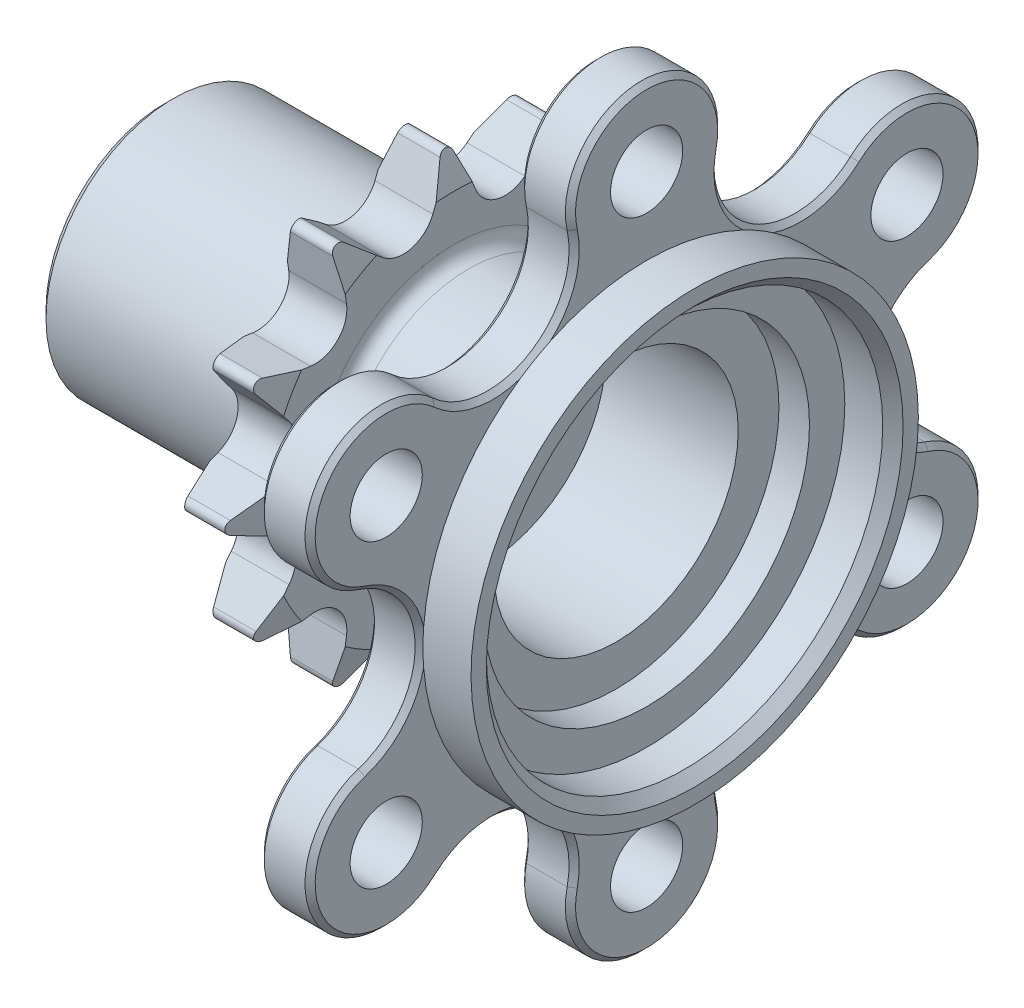
SolidWorks part; units mm, degrees
note: '?' marks a value the reader was unsure of.
material "AISI 4130 Steel, annealed at 865C"
ref_plane "X-Y Datum" through (0, 0, 0) normal (0, 0, 1) x (1, 0, 0)
ref_plane "X-Z Datum" through (0, 0, 0) normal (0, 1, 0) x (1, 0, 0)
ref_plane "Y-Z Datum" through (0, 0, 0) normal (1, 0, 0) x (0, 0, -1)
sketch "Sketch1" plane through (0, 0, 0) normal (1, 0, 0) x (0, 0, -1)
  circle A0 centre (0, 0) radius 47
  dimension "D1" = 94
extrude "Base-Extrude" add sketch "Sketch1" against normal blind 6.35
hole_wizard "M8 Clearance Holes" positions "Sketch5" profile "Sketch7" hole size "M8" standard "ANSI Metric" end condition through all
sketch "Sketch5" plane through (0, 0, 0) normal (1, 0, 0) x (0, 0, -1)
  point P0 (0, -37.5)
  dimension "D1" = 37.5
sketch "Sketch7" plane through (0, -37.5, 0) normal (0, 1, 0) x (0, 0, -1)
  line L0 (0, 0) -> (0, 6.35)
  line L1 (0, 6.35) -> (4.5, 6.35)
  line L2 (4.5, 6.35) -> (4.5, 0)
  line L5 (4.5, 0) -> (0, 0)
  line L11 (0, -6.35) -> (0, 107.95) construction
  dimension "Thru Hole Dia." = 9
  dimension "Thru Hole Depth" = 6.35
pattern_circular "CirPattern" count 6 over 360 about axis through (0, 0, 0) along (1, 0, 0) of "M8 Clearance Holes"
sketch "Sketch19" plane through (0, 0, 0) normal (1, 0, 0) x (0, 0, -1)
  line L0 (0, 37.5) -> (32.476, 18.75) construction
  circle A0 centre (0, 37.5) radius 9.5
  circle A1 centre (32.476, 18.75) radius 9.5
  circle A2 centre (0, 0) radius 47 construction
  arc A3 (9.2748, 35.4439) -> (26.0579, 25.7542) centre (19.194, 33.245) ccw
  circle A4 centre (32.476, 18.75) radius 9.5
  circle A5 centre (32.476, -18.75) radius 9.5
  arc A6 (35.3328, 9.6897) -> (35.3328, -9.6897) centre (38.3881, 0) ccw
  circle A7 centre (32.476, -18.75) radius 9.5
  circle A8 centre (0, -37.5) radius 9.5
  arc A9 (26.0579, -25.7542) -> (9.2748, -35.4439) centre (19.194, -33.245) ccw
  circle A10 centre (0, -37.5) radius 9.5
  circle A11 centre (-32.476, -18.75) radius 9.5
  arc A12 (-9.2748, -35.4439) -> (-26.0579, -25.7542) centre (-19.194, -33.245) ccw
  circle A13 centre (-32.476, -18.75) radius 9.5
  circle A14 centre (-32.476, 18.75) radius 9.5
  arc A15 (-35.3328, -9.6897) -> (-35.3328, 9.6897) centre (-38.3881, 0) ccw
  circle A16 centre (-32.476, 18.75) radius 9.5
  circle A17 centre (0, 37.5) radius 9.5
  arc A18 (-26.0579, 25.7542) -> (-9.2748, 35.4439) centre (-19.194, 33.245) ccw
  circle A19 centre (-32.476, 18.75) radius 4.5 construction
  circle M12 centre (0, 0) radius 47
  dimension "D1" = 10.16
  dimension "D2" = 6
extrude "Cut-Extrude" cut sketch "Sketch19" against normal through all both and the other way through all contours A16 A18 A0 M12 | A0 A3 A1 M12 | A13 A15 A14 M12 | A4 A6 A5 M12 | A7 A9 A8 M12 | A10 A12 A11 M12 | L0 A3
chamfer "Chamfer1" distance 0.635 angle 45 12 edges at (-6.35, 0, 28.2281) (-6.35, -23.5, 40.7032) (-6.35, 23.5, 40.7032) (-6.35, -24.4462, 14.114) (-6.35, 24.4462, 14.114) (-6.35, -47, 0) (-6.35, 47, 0) (-6.35, -24.4462, -14.114) (-6.35, -23.5, -40.7032) (-6.35, 0, -28.2281) (-6.35, 23.5, -40.7032) (-6.35, 24.4462, -14.114)
sketch "Sketch8" plane through (-6.35, 0, 0) normal (-1, 0, 0) x (0, 0, 1)
  circle A0 centre (0, 0) radius 15.875
  dimension "D1" = 31.75
extrude "Shaft-Extrude" add sketch "Sketch8" along normal blind 53.69
ref_plane "Plane2" through (-24, 0, 0) normal (-1, 0, 0) x (0, 0, 1)
sketch "Sketch33" plane through (0, 0, 0) normal (0, 1, 0) x (1, 0, 0)
  line L0 (-24, 45.475) -> (-24, -45.475) construction
  line L1 (-24, 0) -> (-31.214, 0)
  line L2 (-24, 0) -> (-24, 27.5082)
  line L3 (-24, 27.5082) -> (-31.214, 27.5082)
  line L4 (-31.214, 0) -> (-31.214, 27.5082)
  dimension "D1" = 7.214
  dimension "D2" = 27.5082
revolve "Revolve1" add sketch "Sketch33" angle 360 about L1
sketch "Sketch41" plane through (-24, 0, 0) normal (-1, 0, 0) x (0, 0, 1)
  point P0 (0, 0)
sketch "Sketch40" plane through (-24, -33.5661, 0) normal (-1, 0, 0) x (0, 0, 1)
  line L1 (-0.8057, 60.5258) -> (-2.6638, 55.8121)
  line L2 (-6.3502, 57.2652) -> (0, 33.5661) construction
  line L3 (-12.7821, 57.3168) -> (-8.8161, 54.1636)
  arc A1 (0, 61.0743) -> (-0.8057, 60.5258) centre (0, 60.2082) ccw
  arc A2 (-13.7541, 57.3889) -> (-12.7821, 57.3168) centre (-13.3211, 56.6389) cw
  arc A3 (-2.6638, 55.8121) -> (-8.8161, 54.1636) centre (-6.3502, 57.2652) cw
  arc A4 (0, 61.0743) -> (-13.7541, 57.3889) centre (0, 33.5661) ccw
extrude "Cut-Extrude1" cut sketch "Sketch40" along normal through all
sketch "Sketch44" plane through (0, 0, 0) normal (0, 1, 0) x (1, 0, 0)
  line L0 (25.0524, 0) -> (-95.9957, 0)
ref_axis "Axis1" through (25.0524, 0, 0) along (-1, 0, 0)
pattern_circular "CirPattern1" count 12 over 360 about axis through (0, 0, 0) along (1, 0, 0) of "Cut-Extrude1"
chamfer "Chamfer3" distance 0.635 angle 45 12 edges at (0, -23.5, 40.7032) (0, 0, 28.2281) (0, -24.4462, 14.114) (0, 23.5, 40.7032) (0, -47, 0) (0, 24.4462, 14.114) (0, -24.4462, -14.114) (0, 47, 0) (0, 24.4462, -14.114) (0, -23.5, -40.7032) (0, 0, -28.2281) (0, 23.5, -40.7032)
hole_wizard "M10 Tap" positions "Sketch13" profile "Sketch14" tap size "M10x1.5" standard "ANSI Metric"
sketch "Sketch13" plane through (-60.04, 0, 0) normal (-1, 0, 0) x (0, 0, 1)
  point P0 (0, 0)
sketch "Sketch14" plane through (-60.04, 0, 0) normal (0, 1, 0) x (0, 0, 1)
  line L0 (0, 0) -> (0, 62.5927)
  line L1 (0, 62.5927) -> (4.25, 60.039)
  line L2 (4.25, 60.039) -> (4.25, 0.775)
  line L3 (4.25, 0.775) -> (5.025, 0)
  line L5 (5.025, 0) -> (0, 0)
  line L6 (-4.25, 0.775) -> (-5.025, 0) construction
  line L10 (0, 62.5927) -> (-4.25, 60.039) construction
  line L11 (0, -6.35) -> (0, 107.95) construction
  dimension "Tap Drill Dia." = 8.5
  dimension "Tap Drill Depth" = 60.039
  dimension "Near C'Sink Dia." = 10.05
  dimension "Near C'Sink Angle" = 90
  dimension "Drill Angle" = 118
cosmetic thread "Hole Thread2" parameters "D1"=25.4, "D2"=10
chamfer "Shaft Chamfer" distance 1 angle 45 1 edges at (-60.04, 0, 15.875)
sketch "Sketch22" [suppressed] plane through (-6.35, 0, 0) normal (-1, 0, 0) x (0, 0, 1)
  circle A0 centre (32.476, 18.75) radius 6.1
  circle A1 centre (32.476, -18.75) radius 6.1
  circle A2 centre (0, -37.5) radius 6.1
  circle A3 centre (0, 37.5) radius 6.1
  circle A4 centre (-32.476, 18.75) radius 6.1
  circle A5 centre (-32.476, -18.75) radius 6.1
  dimension "D1" = 12.2
split line "Split Line1" [suppressed]
split line "Split Line2"
sketch "Sketch22<2>" [suppressed] plane through (-6.35, 0, 0) normal (-1, 0, 0) x (0, 0, 1) same geometry as "Sketch22"?
sketch "Sketch30" plane through (0, 0, 0) normal (1, 0, 0) x (0, 0, -1)
  circle A0 centre (0, 0) radius 27.8994
  circle A1 centre (0, 0) radius 24.7244
extrude "Lip Extrude" add sketch "Sketch30" along normal blind 5.9995
chamfer "Lip Chamfer" distance 1.27 angle 45 1 edges at (5.9995, 0, -24.7244)
fillet "Fillet2" radius 3 1 edges at (-6.35, 0, -15.875)
fillet "Fillet3" radius 1.778 2 edges at (-24, 0, -15.875) (-31.214, 0, 15.875)
sketch "Sketch45" plane through (0, 0, 0) normal (0, 1, 0) x (1, 0, 0)
  line L0 (-31.214, 27.5082) -> (-30.1095, 27.5082)
  line L1 (-30.1095, 27.5082) -> (-31.214, 23.3861)
  line L2 (-31.214, 23.3861) -> (-31.214, 27.5082)
  line L3 (-27.607, 49.2507) -> (-27.607, 66.7037) construction
  line L4 (-24, 27.5082) -> (-25.1045, 27.5082)
  line L5 (-24, 23.3861) -> (-24, 27.5082)
  line L6 (-25.1045, 27.5082) -> (-24, 23.3861)
  line L7 (-38.1824, 21.7425) -> (-90.3055, 21.7425) construction
  line L8 (-24, 27.5082) -> (-31.214, 27.5082) construction
  line L9 (-24, 45.475) -> (-24, -45.475) construction
  line L10 (-31.214, 22.246) -> (-31.214, 26.9597) construction
  line L12 (-31.214, 20.5975) -> (-31.214, 23.7507) construction
  dimension "D1" = 1.1045
  dimension "D2" = 4.1221
revolve "Cut-Revolve1" cut sketch "Sketch45" angle 360 about axis through (25.0524, 0, 0) along (-1, 0, 0)
sketch "Sketch46" plane through (0, 0, 0) normal (1, 0, 0) x (0, 0, -1)
  circle A0 centre (0, 0) radius 15.24
  dimension "D1" = 30.48
extrude "Cut-Extrude2" cut sketch "Sketch46" along a picked direction on the side against the normal blind 20.32
sketch "Sketch47" plane through (0, 0, 0) normal (1, 0, 0) x (0, 0, -1)
  circle A0 centre (0, 0) radius 20.32
extrude "Cut-Extrude3" cut sketch "Sketch47" along direction (-1, 0, 0) on the side against the normal offset from surface (3.81 mm away) 2.54 up to face at (-6.35, 0, -18.875)
